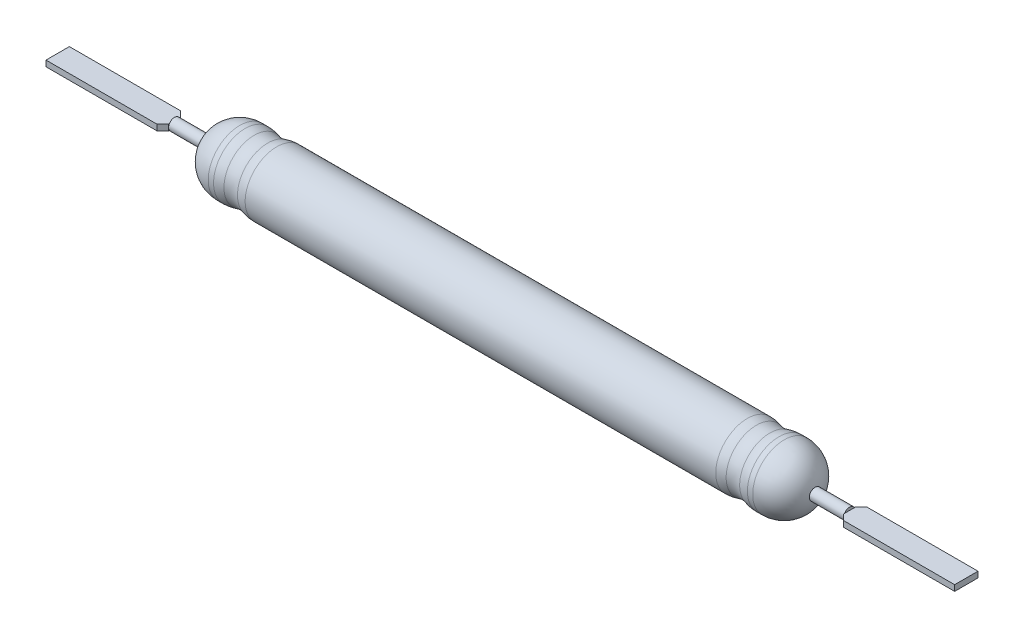
SolidWorks part; units mm, degrees
ref_plane "Спереди" through (0, 0, 0) normal (0, 0, 1) x (1, 0, 0)
ref_plane "Сверху" through (0, 0, 0) normal (0, 1, 0) x (1, 0, 0)
ref_plane "Справа" through (0, 0, 0) normal (1, 0, 0) x (0, 0, -1)
sketch "Эскиз3" plane through (0, 0, 0) normal (0, 1, 0) x (1, 0, 0)
  line L0 (48.855, 2.7) -> (49.31, 2.7)
  line L1 (0, 0) -> (52, 0)
  line L2 (0, 0) -> (0, 0.01)
  line L3 (2.69, 2.7) -> (3.145, 2.7)
  line L4 (52, 0) -> (52, 0.01)
  line L5 (5.855, 2.7) -> (46.145, 2.7)
  arc A0 (49.31, 2.7) -> (52, 0.01) centre (49.31, 0.01) cw
  arc A1 (2.69, 2.7) -> (0, 0.01) centre (2.69, 0.01) ccw
  arc A2 (3.9222, 2.5853) -> (5.0778, 2.5853) centre (4.5, 4.5) ccw
  arc A3 (48.0778, 2.5853) -> (46.9222, 2.5853) centre (47.5, 4.5) cw
  arc A4 (48.855, 2.7) -> (48.0778, 2.5853) centre (48.855, 0.01) ccw
  arc A5 (46.9222, 2.5853) -> (46.145, 2.7) centre (46.145, 0.01) ccw
  arc A6 (5.855, 2.7) -> (5.0778, 2.5853) centre (5.855, 0.01) ccw
  arc A7 (3.9222, 2.5853) -> (3.145, 2.7) centre (3.145, 0.01) ccw
  point P7 (52, 2.7)
  point P10 (0, 2.7)
  point P19 (48.3718, 2.7)
  point P24 (5.3718, 2.7)
  dimension "D3" = 2.69
  dimension "D4" = 4.5
  dimension "D5" = 4
  dimension "D6" = 4.5
  dimension "D7" = 2.69
  dimension "D1" = 2.7
  dimension "D2" = 52
sketch "Эскиз4" plane through (0, 0, 0) normal (1, 0, 0) x (0, 0, -1)
  circle A0 centre (0, 0) radius 2.7
sweep "По траектории1" add profiles "Эскиз3" path "Эскиз4"
sketch "Эскиз5" plane through (0, 0, 0) normal (0, 1, 0) x (1, 0, 0)
  line L0 (-2.31, 0) -> (54.31, 0) construction
  line L1 (49.31, 2.7) -> (49.31, -2.7) construction
  line L2 (54.9, 0) -> (51.9, 0)
  line L3 (54.9, 0) -> (54.9, 0.5)
  line L4 (54.9, 0.5) -> (51.9, 0.5)
  line L5 (51.9, 0) -> (51.9, 0.5)
  line L6 (-2.9, 0) -> (54.9, 0)
  line L8 (0.1, 0) -> (0.1, 0.5)
  line L9 (-2.9, 0.5) -> (0.1, 0.5)
  line L10 (-2.9, 0) -> (-2.9, 0.5)
  line L11 (-2.9, 0) -> (0.1, 0)
  point P0 (0, 0)
  dimension "D1" = 0.5
  dimension "D2" = 3
  dimension "D3" = 2.9
  dimension "D4" = 5
sketch "Эскиз6" plane through (0, 0, 0) normal (1, 0, 0) x (0, 0, -1)
  circle A0 centre (0, 0) radius 3.1682
ref_plane "Плоскость4" through (-2.9, 0, 0) normal (1, 0, 0) x (0, 0, -1)
sketch "Эскиз7" plane through (-2.9, 0, 0) normal (1, 0, 0) x (0, 0, -1)
  circle A0 centre (0, 0) radius 0.5
extrude "Бобышка-Вытянуть1" add sketch "Эскиз7" along normal blind 57.8
sketch "Эскиз8" plane through (-2.9, 0, 0) normal (-1, 0, 0) x (0, 0, 1)
  line L1 (-1, 0.25) -> (1, 0.25)
  line L2 (-1, 0.25) -> (-1, -0.25)
  line L3 (-1, -0.25) -> (1, -0.25)
  line L4 (1, 0.25) -> (1, -0.25)
  circle A0 centre (0, 0) radius 0.5 construction
  point P4 (0, -0.25)
  point P7 (1, 0)
  dimension "D1" = 2
  dimension "D2" = 0
  dimension "D3" = 0.5
  dimension "D4" = 0
extrude "Бобышка-Вытянуть2" add sketch "Эскиз8" along normal blind 10
chamfer "Фаска1" distance 0.5 angle 45 2 edges at (-2.9, 0, -1) (-2.9, 0, 1)
sketch "Эскиз9" plane through (54.9, 0, 0) normal (1, 0, 0) x (0, 0, -1)
  line L1 (1, 0.25) -> (-1, 0.25)
  line L2 (1, 0.25) -> (1, -0.25)
  line L3 (1, -0.25) -> (-1, -0.25)
  line L4 (-1, 0.25) -> (-1, -0.25)
extrude "Бобышка-Вытянуть3" add sketch "Эскиз9" along normal blind 10
chamfer "Фаска2" distance 0.5 angle 45 2 edges at (54.9, 0, 1) (54.9, 0, -1)
